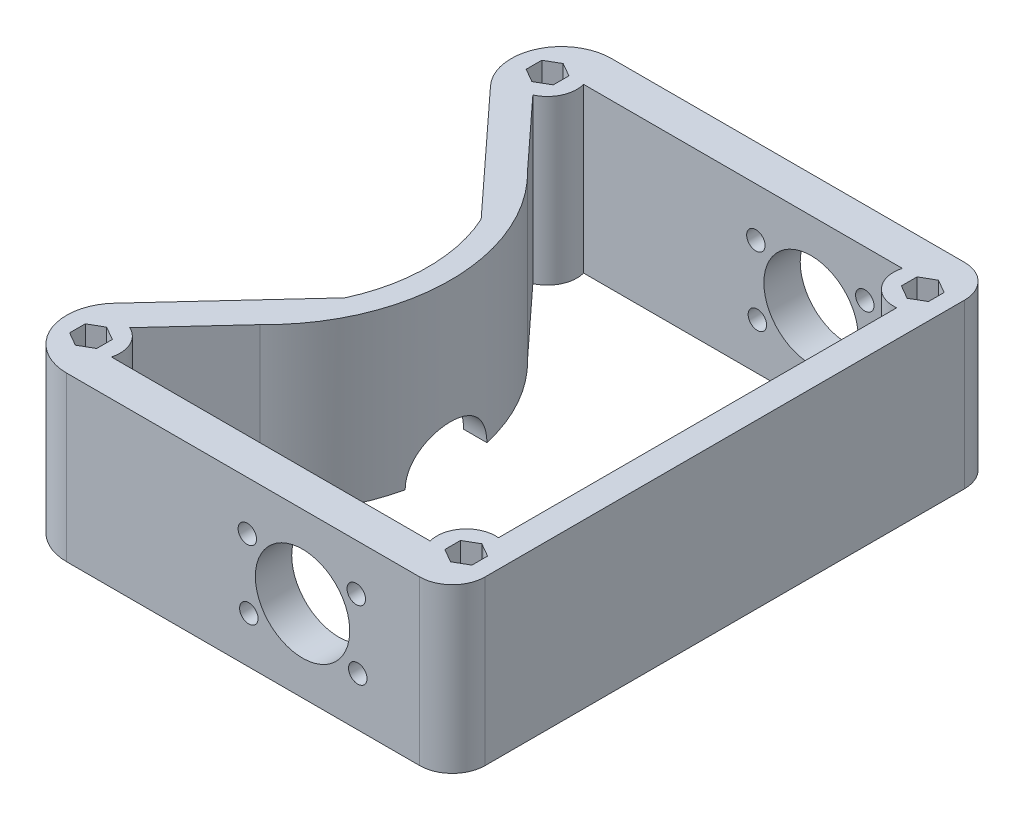
SolidWorks part; units mm, degrees
material "TPU"
ref_plane "Front Plane" through (0, 0, 0) normal (0, 0, 1) x (1, 0, 0)
ref_plane "Top Plane" through (0, 0, 0) normal (0, 1, 0) x (1, 0, 0)
ref_plane "Right Plane" through (0, 0, 0) normal (1, 0, 0) x (0, 0, -1)
sketch "Sketch1" plane through (0, 0, 0) normal (0, 1, 0) x (1, 0, 0)
  line L0 (66.675, 17.145) -> (66.675, 128.905) construction
  line L1 (-28.575, 9.525) -> (66.675, 9.525)
  line L2 (-28.575, 9.525) -> (-28.575, 17.9917)
  line L3 (-28.575, 17.9917) -> (66.675, 17.9917)
  line L4 (66.675, 9.525) -> (66.675, 17.9917)
  line L5 (-28.575, 9.525) -> (66.675, 17.9917) construction
  line L6 (-28.575, 17.9917) -> (66.675, 9.525) construction
  line L9 (-28.575, 9.525) -> (59.055, 9.525) construction
  point P0 (19.05, 13.7583)
  point P15 (19.05, 9.525)
  dimension "D1" = 95.25
  dimension "D2" = 8.4667
extrude "Boss-Extrude1" add sketch "Sketch1" along normal blind 38.1
sketch "Sketch2" plane through (0, 38.1, 0) normal (0, 1, 0) x (1, 0, 0)
  line L1 (60.325, 9.525) -> (66.675, 9.525)
  line L2 (60.325, 9.525) -> (60.325, 136.525)
  line L3 (60.325, 136.525) -> (66.675, 136.525)
  line L4 (66.675, 9.525) -> (66.675, 136.525)
  line L6 (32.8756, 15.875) -> (32.8756, 130.175) construction
  line L7 (-20.4, 15.875) -> (58.5, 15.875) construction
  line L8 (58.5, 130.175) -> (-20.4, 130.175) construction
  dimension "D1" = 127
  dimension "D2" = 6.35
extrude "Boss-Extrude2" add sketch "Sketch2" against normal up to surface (38.1 mm away) up to face at (19.05, 0, -13.7583)
sketch "Sketch3" plane through (0, 38.1, 0) normal (0, 1, 0) x (1, 0, 0)
  line L0 (-28.575, 17.9917) -> (-28.575, 9.525) construction
  line L1 (60.325, 136.525) -> (-28.575, 136.525)
  line L2 (60.325, 136.525) -> (60.325, 128.0583)
  line L3 (60.325, 128.0583) -> (-28.575, 128.0583)
  line L4 (-28.575, 136.525) -> (-28.575, 128.0583)
extrude "Boss-Extrude3" add sketch "Sketch3" against normal up to surface (38.1 mm away) up to face at (32.8083, 0, -54.6806)
sketch "Sketch4" plane through (0, 0, -136.525) normal (0, 0, -1) x (-1, 0, 0)
  line L0 (3.175, 38.1) -> (-66.675, 38.1) construction
  line L1 (-66.675, 19.05) -> (3.175, 19.05) construction
  line L2 (-66.675, 0) -> (-66.675, 38.1) construction
  line L5 (28.575, 19.05) -> (3.175, 19.05) construction
  line L6 (28.575, 0) -> (28.575, 38.1) construction
  circle A0 centre (-31.75, 19.05) radius 11
  point P7 (-31.75, 38.1)
  dimension "D1" = 22
  dimension "D2" = 25.4
extrude "Cut-Extrude1" cut sketch "Sketch4" against normal through all contours A0 region at (31.75, 19.05, -136.525)
sketch "Sketch5" plane through (0, 0, -136.525) normal (0, 0, -1) x (-1, 0, 0)
  circle A0 centre (-18.8777, 26.7049) radius 2.1527
  circle A1 centre (-19.2285, 10.8337) radius 2.1527
  circle A2 centre (-44.6223, 11.3951) radius 2.1527
  circle A3 centre (-44.2715, 27.2663) radius 2.1526
  circle A4 centre (-44.6223, 11.3951) radius 2.1527 construction
  circle A5 centre (-18.8777, 26.7049) radius 2.1526 construction
  circle A6 centre (-19.2285, 10.8337) radius 2.1527 construction
  circle A9 centre (-44.2715, 27.2663) radius 2.1526 construction
extrude "Cut-Extrude2" cut sketch "Sketch5" against normal through all
fillet "Fillet1" radius 7.62 2 edges at (66.675, 19.05, -9.525) (66.675, 19.05, -136.525)
sketch "Sketch10" plane through (0, 38.1, 0) normal (0, 1, 0) x (1, 0, 0)
  line L0 (-28.575, 9.525) -> (59.055, 9.525) construction
  line L2 (-28.575, 17.9917) -> (-28.575, 9.525)
  line L5 (66.675, 73.025) -> (-147.9374, 73.025) construction
  line L7 (-28.575, 136.525) -> (-34.925, 136.525)
  line L11 (-34.925, 25.781) -> (-5.996, 57.15)
  line L15 (-28.575, 17.9917) -> (-28.575, 22.225)
  line L16 (-28.575, 22.225) -> (-10.4944, 41.8306)
  line L17 (-28.575, 123.825) -> (-10.4944, 104.2194)
  line L18 (-34.925, 120.269) -> (-5.996, 88.9)
  line L19 (-10.4944, 41.8306) -> (-5.996, 57.15) construction
  line L22 (-28.575, 136.525) -> (-28.575, 123.825)
  line L26 (-34.925, 136.525) -> (-34.925, 120.269)
  line L27 (-34.925, 25.781) -> (-34.925, 9.525)
  line L28 (-34.925, 9.525) -> (-28.575, 9.525)
  line L29 (66.675, 17.145) -> (66.675, 128.905) construction
  arc A0 (-5.996, 57.15) -> (-5.996, 88.9) centre (-40.6312, 73.025) ccw
  arc A2 (-10.4944, 104.2194) -> (-10.4944, 41.8306) centre (-40.6312, 73.025) cw
  dimension "D7" = 31.75
  dimension "D6" = 38.1
  dimension "D1" = 16.256
  dimension "D2" = 6.35
  dimension "D3" = 12.7
  dimension "D4" = 42.672
  dimension "D5" = 26.67
extrude "Boss-Extrude4" add sketch "Sketch10" against normal up to surface (38.1 mm away) up to face at (26.0966, 0, -73.025)
sketch "Sketch12" plane through (60.325, 0, 0) normal (-1, 0, 0) x (0, 0, 1)
  line L0 (-88.9, 0) -> (-82.55, 0) construction
  line L1 (-88.9, 0) -> (-57.15, 0) construction
  line L2 (-57.15, 0) -> (-63.5, 0) construction
  line L3 (-82.55, 0) -> (-63.5, 0)
  arc A0 (-82.55, 0) -> (-63.5, 0) centre (-73.025, 0) cw
  dimension "D1" = 19.05
extrude "Cut-Extrude8" cut sketch "Sketch12" along normal up to surface (95.25 mm away) up to face at (-34.925, 19.05, -128.397)
fillet "Fillet2" 2 edges at (-34.925, 19.05, -120.269) (-34.925, 19.05, -136.525) type full round first side face at (-20.4605, 19.05, -104.5845) second side face at (42.1188, 27.2663, -136.525) middle face at (-34.925, 19.05, -128.397)
fillet "Fillet3" 2 edges at (-34.925, 19.05, -25.781) (-34.925, 19.05, -9.525) type full round first side face at (-20.4605, 19.05, -41.4655) second side face at (42.1188, 27.2663, -9.525) middle face at (-34.925, 19.05, -17.653)
fillet "Fillet4" radius 6.35 2 edges at (60.325, 19.05, -128.0583) (60.325, 19.05, -17.9917)
sketch "Sketch15" plane through (0, 38.1, 0) normal (0, 1, 0) x (1, 0, 0)
  line L0 (-2.5312, 73.025) -> (66.675, 73.025) construction
  line L1 (66.675, 17.145) -> (66.675, 128.905) construction
  line L2 (-27.8745, 23.4708) -> (-27.8745, 26.6458) construction
  line L3 (-24.6995, 21.6377) -> (-27.8745, 23.4708)
  line L4 (-27.8745, 23.4708) -> (-31.0495, 21.6377)
  line L5 (-31.0495, 21.6377) -> (-31.0495, 17.9716)
  line L6 (-31.0495, 17.9716) -> (-27.8745, 16.1385)
  line L7 (-27.8745, 16.1385) -> (-24.6995, 17.9716)
  line L8 (-24.6995, 17.9716) -> (-24.6995, 21.6377)
  line L9 (-33.9426, 16.5233) -> (63.5, 69.215) construction
  line L10 (63.5, 69.215) -> (63.5, 9.525) construction
  line L11 (59.6245, 129.9115) -> (56.4495, 128.0784)
  line L12 (59.055, 9.525) -> (63.5, 9.525) construction
  line L13 (60.325, 69.215) -> (66.675, 69.215) construction
  line L14 (60.325, 121.7083) -> (60.325, 24.3417) construction
  line L15 (-24.6995, 128.0784) -> (-24.6995, 124.4123)
  line L16 (-27.8745, 129.9115) -> (-24.6995, 128.0784)
  line L17 (-31.0495, 128.0784) -> (-27.8745, 129.9115)
  line L18 (-31.0495, 124.4123) -> (-31.0495, 128.0784)
  line L19 (-27.8745, 122.5792) -> (-31.0495, 124.4123)
  line L20 (-24.6995, 124.4123) -> (-27.8745, 122.5792)
  line L21 (15.875, 120.6024) -> (15.875, 25.4476) construction
  line L22 (62.7995, 128.0784) -> (59.6245, 129.9115)
  line L23 (62.7995, 124.4123) -> (62.7995, 128.0784)
  line L24 (-34.925, 124.8361) -> (-34.925, 21.2139) construction
  line L25 (-34.925, 73.025) -> (66.675, 73.025) construction
  line L26 (59.6245, 122.5792) -> (62.7995, 124.4123)
  line L27 (56.4495, 124.4123) -> (59.6245, 122.5792)
  line L28 (56.4495, 128.0784) -> (56.4495, 124.4123)
  line L29 (56.4495, 17.9716) -> (56.4495, 21.6377)
  line L30 (59.6245, 16.1385) -> (56.4495, 17.9716)
  line L31 (62.7995, 17.9716) -> (59.6245, 16.1385)
  line L32 (62.7995, 21.6377) -> (62.7995, 17.9716)
  line L33 (59.6245, 23.4708) -> (62.7995, 21.6377)
  line L34 (56.4495, 21.6377) -> (59.6245, 23.4708)
  arc A2 (-26.2521, 22.5744) -> (-29.4271, 22.5744) centre (-27.8396, 19.8248) ccw construction
  circle A3 centre (59.6245, 126.2454) radius 6.8412
  arc A4 (-5.996, 57.15) -> (-5.996, 88.9) centre (-40.6312, 73.025) ccw construction
  circle A7 centre (-27.8745, 19.8046) radius 6.8412
  arc A8 (-31.8288, 29.1383) -> (-23.2361, 9.525) centre (-23.2361, 21.2139) ccw construction
  circle A9 centre (-27.8745, 19.8046) radius 3.175 construction
  circle A10 centre (-27.8745, 126.2454) radius 6.8412
  arc A11 (-23.2361, 136.525) -> (-31.8288, 116.9117) centre (-23.2361, 124.8361) ccw construction
  circle A12 centre (59.6245, 19.8046) radius 6.8412
  point P49 (15.875, 73.025)
  line M11 (60.325, 121.7083) -> (60.325, 24.3417)
  arc M12 (60.325, 24.3417) -> (53.975, 17.9917) centre (53.975, 24.3417) cw
  line M13 (53.975, 17.9917) -> (-28.575, 17.9917)
  line M15 (-28.575, 22.225) -> (-10.4944, 41.8306)
  line M17 (-10.4944, 104.2194) -> (-28.575, 123.825)
  line M19 (-28.575, 128.0583) -> (53.975, 128.0583)
  arc M20 (53.975, 128.0583) -> (60.325, 121.7083) centre (53.975, 121.7083) cw
  dimension "D1" = 3.175
  dimension "D2" = 3.81
extrude "Boss-Extrude7" add sketch "Sketch15" against normal up to surface (38.1 mm away) contours A7 L8 L7 L6 L5 L4 L3 M15 M13 | A7 L3 L8 M13 M15 | A12 L29 L34 L33 M13 M12 M11 | A12 L33 L32 L31 L30 L29 M11 M12 M13 | A3 L28 L11 L22 L23 L26 M11 M19 M20 | A3 L26 L27 L28 M19 M11 M20 | A10 L20 L19 L18 L17 L16 L15 M17 M19 | A10 L15 L20 M19 M17 region at (-23.7078, 38.1, -21.8223) region at (-27.6323, 38.1, -23.5524) region at (-23.7078, 38.1, -124.2277) region at (-22.9887, 38.1, -128.2501) region at (56.2108, 38.1, -123.4706) region at (60.5165, 38.1, -120.5742) region at (56.2108, 38.1, -22.5794) region at (53.5014, 38.1, -17.8001) up to face at (8.9564, 0, -73.025)
sketch "Sketch21" plane through (0, 38.1, 0) normal (0, 1, 0) x (1, 0, 0)
  line L1 (-24.6995, 21.6377) -> (-27.857, 23.4608)
  line L2 (-27.857, 23.4608) -> (-31.0146, 21.6377)
  line L3 (-31.0146, 21.6377) -> (-31.0146, 17.9917)
  line L4 (-31.0146, 17.9917) -> (-27.857, 16.1686)
  line L5 (-27.857, 16.1686) -> (-24.6995, 17.9917)
  line L6 (-24.6995, 17.9917) -> (-24.6995, 21.6377)
  line L7 (2.7429, 73.025) -> (60.325, 73.025) construction
  line L8 (60.325, 119.4401) -> (60.325, 26.6099) construction
  line L9 (15.875, 120.6024) -> (15.875, 25.4476) construction
  line L10 (56.4495, 17.9917) -> (56.4495, 21.6377)
  line L11 (59.607, 16.1686) -> (56.4495, 17.9917)
  line L12 (62.7646, 17.9917) -> (59.607, 16.1686)
  line L13 (62.7646, 21.6377) -> (62.7646, 17.9917)
  line L14 (59.607, 23.4608) -> (62.7646, 21.6377)
  line L15 (56.4495, 21.6377) -> (59.607, 23.4608)
  line L16 (59.607, 129.8814) -> (56.4495, 128.0583)
  line L17 (62.7646, 128.0583) -> (59.607, 129.8814)
  line L18 (62.7646, 124.4123) -> (62.7646, 128.0583)
  line L19 (59.607, 122.5892) -> (62.7646, 124.4123)
  line L20 (56.4495, 124.4123) -> (59.607, 122.5892)
  line L21 (56.4495, 128.0583) -> (56.4495, 124.4123)
  line L22 (-24.6995, 128.0583) -> (-24.6995, 124.4123)
  line L23 (-27.857, 129.8814) -> (-24.6995, 128.0583)
  line L24 (-31.0146, 128.0583) -> (-27.857, 129.8814)
  line L25 (-31.0146, 124.4123) -> (-31.0146, 128.0583)
  line L26 (-27.857, 122.5892) -> (-31.0146, 124.4123)
  line L27 (-24.6995, 124.4123) -> (-27.857, 122.5892)
  circle A0 centre (-27.857, 19.8147) radius 3.1576 construction
  arc A1 (-10.4944, 41.8306) -> (-10.4944, 104.2194) centre (-40.6312, 73.025) ccw construction
extrude "Cut-Extrude12" cut sketch "Sketch21" against normal through all
